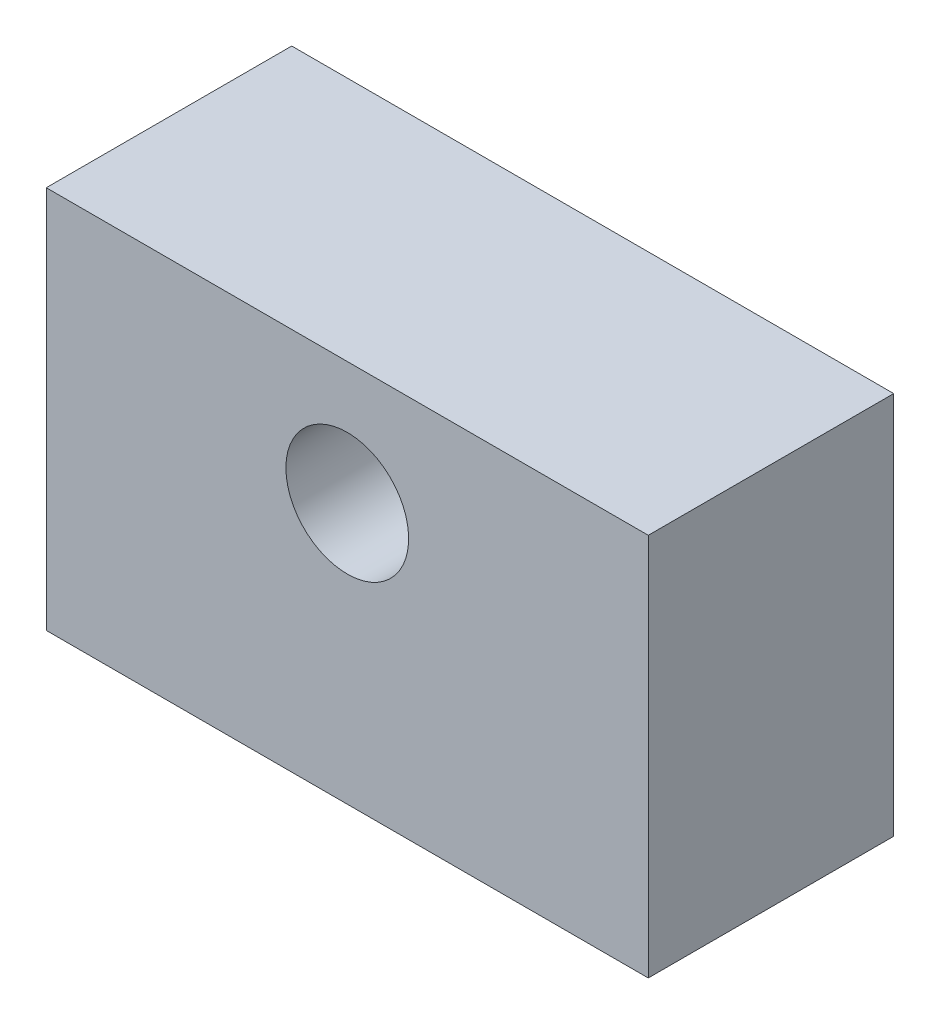
SolidWorks part; units mm, degrees
material "1060 Alloy"
ref_plane "Front" through (0, 0, 0) normal (0, 0, 1) x (1, 0, 0)
ref_plane "Top" through (0, 0, 0) normal (0, 1, 0) x (1, 0, 0)
ref_plane "Right" through (0, 0, 0) normal (1, 0, 0) x (0, 0, -1)
sketch "Sketch3" plane through (0, 0, 0) normal (0, 0, 1) x (1, 0, 0)
  line L0 (-0.127, -6.35) -> (30.1755, -6.35)
  line L1 (0, 0) -> (31.1484, 0)
  line L2 (0, 0) -> (0, -19.8376)
  line L3 (0, -19.8376) -> (31.1484, -19.8376)
  line L4 (31.1484, 0) -> (31.1484, -19.8376)
  line L5 (15.5742, -19.8376) -> (15.5742, 0) construction
  line L6 (15.5742, -6.35) -> (8.0621, -19.3614) construction
  line L15 (12.5496, -11.5887) -> (15.5742, -13.335) construction
  line L16 (15.5742, -6.35) -> (22.9274, -19.0862) construction
  circle A0 centre (15.5742, -6.35) radius 6.0492 construction
  point P14 (0, -6.35)
  point P17 (9.525, -6.35)
  point P19 (31.1484, -6.35)
  point P20 (7.7871, -19.8376)
  point P24 (23.3613, -19.8376)
  dimension "D2" = 6.35
  dimension "D6" = 3.4925
  dimension "D3" = 60
  dimension "D1" = 9.525
  dimension "D4" = 9.525
  dimension "D5" = 60
extrude "Boss-Extrude1" add sketch "Sketch3" along normal mid plane 12.7
sketch "Sketch4" plane through (0, 0, 0) normal (-1, 0, 0) x (0, 0, 1)
  circle A0 centre (0, -6.35) radius 3.175
  dimension "D1" = 6.35
extrude "Cut-Extrude1" cut sketch "Sketch4" against normal blind 9.525
ref_plane "Plane1" through (7.7871, -19.8376, 0) normal (-0.5, -0.866, 0) x (-0.866, 0.5, 0)
ref_plane "Mirror Plane" through (15.5742, 0, 0) normal (-1, 0, 0) x (0, 0, 1)
sketch "Sketch5" plane through (7.7871, -19.8376, 0) normal (-0.5, -0.866, 0) x (-0.866, 0.5, 0)
  circle A0 centre (0, 0) radius 3.175
  dimension "D1" = 6.35
extrude "Cut-Extrude5" cut sketch "Sketch5" against normal blind 9.525 and the other way up to next
sketch "Sketch6" plane through (0, 0, 6.35) normal (0, 0, -1) x (-1, 0, 0)
  circle A0 centre (-15.5742, -6.35) radius 3.175
  dimension "D1" = 6.35
extrude "Cut-Extrude6" cut sketch "Sketch6" along normal blind 9.525
mirror "Mirror1" about plane through (15.5742, 0, 0) normal (-1, 0, 0) of "Cut-Extrude5"
equation "\"truss_member_od\" = .25in"
equation "\"truss_member_id\"= 0in"
equation "\"truss_member_L1\" = 2.125in"
equation "\"connector_hole_depth\" = .375in"
equation "\"D1@Boss-Extrude1\"=\"truss_member_od\"*2"
equation "\"D6@Sketch3\"=\"truss_member_od\"/2*1.1"
equation "\"D1@Sketch4\"=\"truss_member_od\""
equation "\"D1@Cut-Extrude1\"=\"connector_hole_depth\""
equation "\"D1@Sketch3\"=\"connector_hole_depth\""
equation "\"D4@Sketch3\"=\"connector_hole_depth\""
equation "\"D1@Sketch5\"=\"truss_member_od\""
equation "\"D1@Cut-Extrude5\"=\"connector_hole_depth\""
equation "\"D1@Cut-Extrude6\"=\"connector_hole_depth\""
equation "\"D1@Sketch6\"=\"truss_member_od\""
